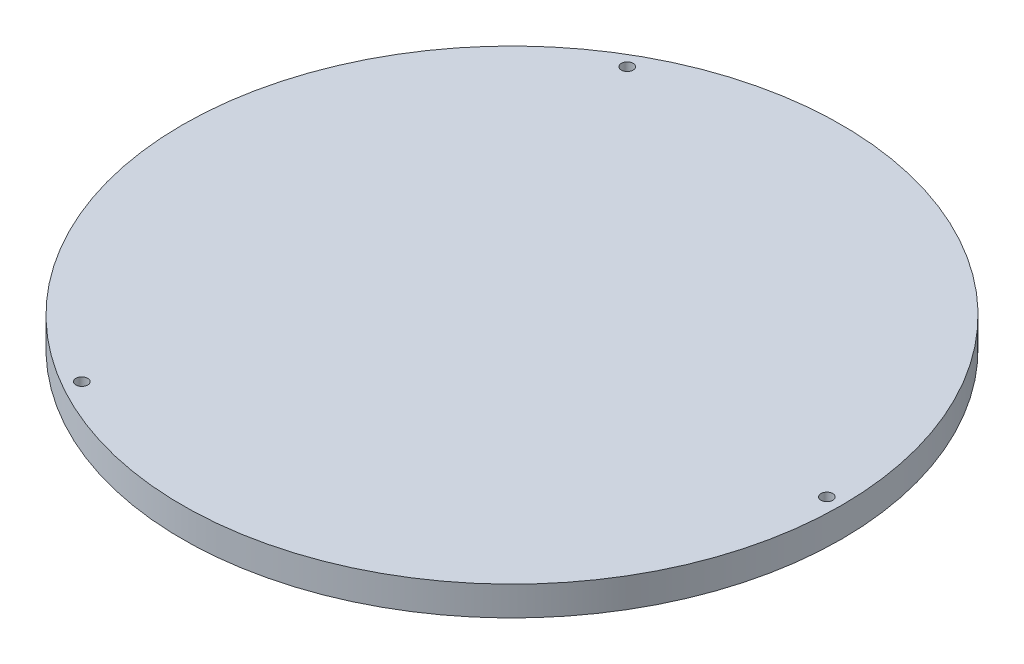
SolidWorks part; units mm, degrees
ref_plane "Front Plane" through (0, 0, 0) normal (0, 0, 1) x (1, 0, 0)
ref_plane "Top Plane" through (0, 0, 0) normal (0, 1, 0) x (1, 0, 0)
ref_plane "Right Plane" through (0, 0, 0) normal (1, 0, 0) x (0, 0, -1)
sketch "Sketch1" plane through (0, 0, 0) normal (0, 0, 1) x (1, 0, 0)
  line L0 (0, -200000) -> (0, 218797.9879) construction
  line L1 (142.875, -24.4122) -> (142.875, -37.1122) construction
  line L2 (0, -24.4122) -> (142.875, -24.4122) construction
  line L3 (142.875, -37.1122) -> (0, -37.1122) construction
  line L4 (0, -200000) -> (0, 218797.9879) construction
  line L5 (142.875, -24.4122) -> (142.875, -37.1122)
  line L6 (0, -24.4122) -> (142.875, -24.4122)
  line L7 (142.875, -37.1122) -> (0, -37.1122)
  line L8 (0, -24.4122) -> (0, -37.1122)
revolve "Revolve1" add sketch "Sketch1" angle 360 about L4
hole_wizard "1/4-20 Tapped Hole1" positions "Sketch2" profile "Sketch3" tap size "1/4-20" standard "ANSI Inch" end condition up to next
sketch "Sketch2" plane through (0, -24.4122, 0) normal (0, 1, 0) x (1, 0, 0)
  line L0 (0, 0) -> (136.525, 0) construction
  line L3 (0, 0) -> (-68.2625, -118.2341) construction
  line L6 (0, 0) -> (-68.2625, 118.2341) construction
  circle A0 centre (0, 0) radius 136.525
  point P0 (136.525, 0)
  point P2 (-68.2625, -118.2341)
  point P4 (-68.2625, 118.2341)
  point P31 (-67.1131, 116.2433)
  dimension "D1" = 120
  dimension "D2" = 120
sketch "Sketch3" plane through (136.525, -24.4122, 0) normal (1, 0, 0) x (0, 0, 1)
  line L0 (0, 0) -> (0, 12.7)
  line L1 (0, 12.7) -> (2.5527, 12.7)
  line L2 (2.5527, 12.7) -> (2.5527, 0)
  line L5 (2.5527, 0) -> (0, 0)
  line L11 (0, -6.35) -> (0, 107.95) construction
  dimension "Thru Tap Drill Dia." = 5.1054
  dimension "Thru Tap Drill Depth" = 12.7
cosmetic thread "Hole Thread1"
cosmetic thread "Hole Thread2"
cosmetic thread "Hole Thread3"
